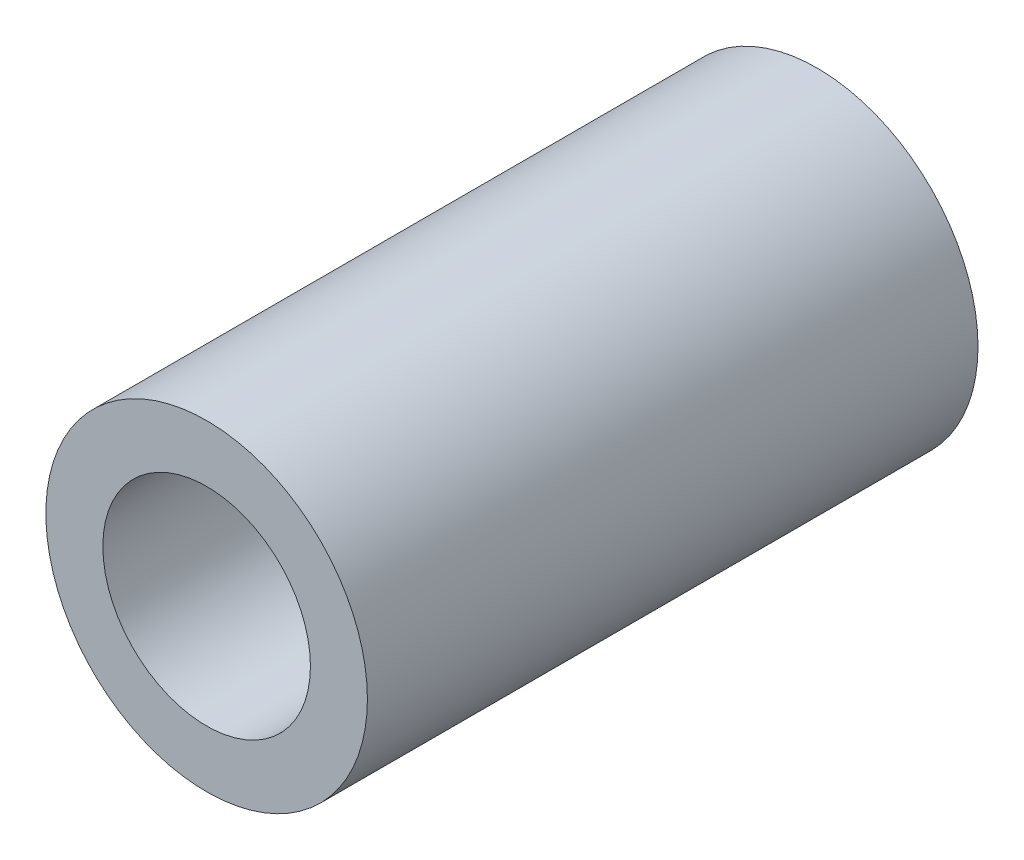
SolidWorks part; units mm, degrees
ref_plane "前视基准面" through (0, 0, 0) normal (0, 0, 1) x (1, 0, 0)
ref_plane "上视基准面" through (0, 0, 0) normal (0, 1, 0) x (1, 0, 0)
ref_plane "右视基准面" through (0, 0, 0) normal (1, 0, 0) x (0, 0, -1)
sketch "草图1" plane through (0, 0, 0) normal (0, 0, 1) x (1, 0, 0)
  circle A0 centre (0, 0) radius 3.95
  circle A1 centre (0, 0) radius 2.55
  circle A2 centre (0, 0) radius 2.7
  dimension "D1" = 7.9
  dimension "D2" = 5.1
  dimension "D3" = 5.4
extrude "凸台-拉伸1" add sketch "草图1" along normal blind 7 contours A0 A2 | A2 A1 region at (-3.8383, 0, 0) region at (-2.6236, 0, 0)
extrude "凸台-拉伸2" add sketch "草图1<3>" against normal blind 8 contours A0 A2 region at (-3.8383, 0, 0)
sketch "草图1<3>" plane through (0, 0, 0) normal (0, 0, 1) x (1, 0, 0) same geometry as "草图1"
